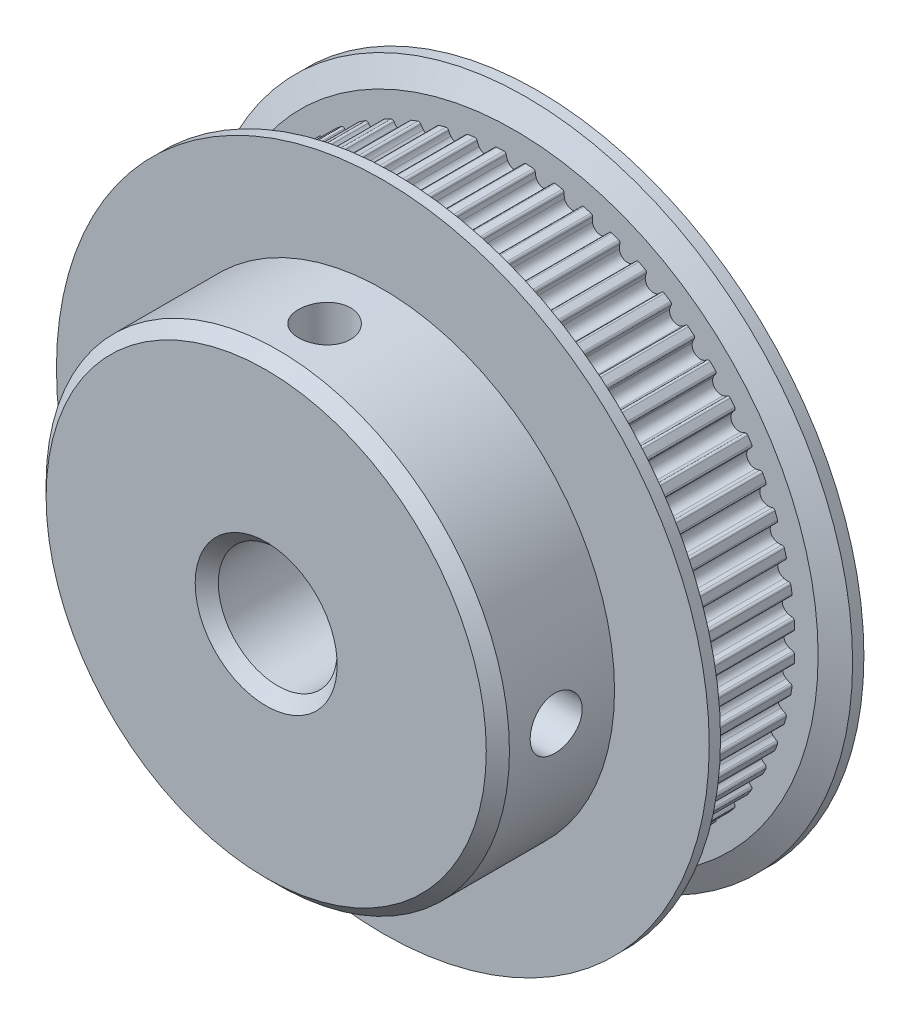
SolidWorks part; units mm, degrees
ref_plane "Front Plane" through (0, 0, 0) normal (0, 0, 1) x (1, 0, 0)
ref_plane "Top Plane" through (0, 0, 0) normal (0, 1, 0) x (1, 0, 0)
ref_plane "Right Plane" through (0, 0, 0) normal (1, 0, 0) x (0, 0, -1)
sketch "Sketch1" plane through (0, 0, 0) normal (0, 0, 1) x (1, 0, 0)
  line L1 (-1.9027, 18.097) -> (1.9027, 18.097) construction
  line L4 (0, 0) -> (0, 18.097) construction
  line L5 (0, 18.097) -> (0, 19.7035) construction
  line L6 (0, 19.101) -> (1.9973, 18.9963) construction
  line L7 (1.9973, 18.9963) -> (2.8966, 18.9017) construction
  line L8 (1.9973, 18.9963) -> (1.9027, 18.097) construction
  line L9 (-1.9973, 18.9963) -> (-1.9027, 18.097) construction
  line L10 (-1.9707, 18.7437) -> (-2.31, 21.971)
  line L11 (-2.31, 21.971) -> (2.31, 21.971)
  line L12 (2.31, 21.971) -> (1.9707, 18.7437)
  circle A0 centre (0, 0) radius 19.101 construction
  circle A1 centre (0, 0) radius 21.971 construction
  circle A2 centre (0, 0) radius 18.847 construction
  arc A3 (-0.4989, 18.4088) -> (0.4989, 18.4088) centre (0, 18.652) ccw
  arc A4 (-0.4989, 18.4088) -> (-0.5897, 18.7039) centre (0.4, 18.847) cw
  arc A5 (-1.9707, 18.7437) -> (-0.7441, 18.8323) centre (0, 0) cw
  arc A6 (-0.5897, 18.7039) -> (-0.7441, 18.8323) centre (-0.7382, 18.6824) ccw
  arc A7 (1.9707, 18.7437) -> (0.7441, 18.8323) centre (0, 0) ccw
  arc A8 (0.5897, 18.7039) -> (0.7441, 18.8323) centre (0.7382, 18.6824) cw
  arc A9 (0.4989, 18.4088) -> (0.5897, 18.7039) centre (-0.4, 18.847) ccw
  point P6 (0, 20.9083)
  point P11 (0, 19.101)
  point P13 (0, 21.971)
  point P14 (0, 18.847)
  dimension "D1" = 1.2049
  dimension "D2" = 0.6025
sketch "Sketch2" plane through (0, 0, 0) normal (1, 0, 0) x (0, 0, -1)
  line L0 (-9.1313, 4) -> (9.1313, 4)
  line L1 (-9.1313, 4) -> (-9.1313, 15.595)
  line L2 (-9.1313, 15.595) -> (-1.2787, 15.595)
  line L3 (-1.2787, 15.595) -> (-1.2787, 21.971)
  line L4 (-1.2787, 21.971) -> (0.2413, 21.971) construction
  line L5 (0.2413, 21.971) -> (0.2413, 18.847) construction
  line L6 (0.2413, 18.847) -> (7.6113, 18.847)
  line L7 (7.6113, 18.847) -> (7.6113, 21.971) construction
  line L8 (7.6113, 21.971) -> (9.1313, 21.971) construction
  line L9 (9.1313, 21.971) -> (9.1313, 4)
  line L10 (-9.1313, 0) -> (9.1313, 0) construction
  line L11 (8.3713, 21.971) -> (7.6113, 20.409)
  line L12 (0.2413, 20.409) -> (-0.5187, 21.971)
  line L13 (-1.2787, 21.971) -> (-0.5187, 21.971)
  line L14 (0.2413, 20.409) -> (0.2413, 18.847)
  line L15 (7.6113, 18.847) -> (7.6113, 20.409)
  line L16 (8.3713, 21.971) -> (9.1313, 21.971)
  arc A0 (0.2413, 20.409) -> (-0.5187, 21.971) centre (-1.7439, 20.409) ccw construction
  arc A1 (7.6113, 20.409) -> (8.3713, 21.971) centre (9.5965, 20.409) cw construction
  point P12 (0.2413, 20.409)
  point P14 (-0.5187, 21.971)
  point P20 (7.6113, 20.409)
  point P21 (8.3713, 21.971)
  point P25 (7.6113, 0)
  point P26 (0.2413, 0)
revolve "Revolve1" add sketch "Sketch2" angle 360 mid plane about L10
sketch "Sketch3" plane through (0, 0, 0) normal (0, 0, 1) x (1, 0, 0)
  line L6 (2.31, 21.971) -> (-2.31, 21.971)
  line L7 (1.9707, 18.7437) -> (2.31, 21.971)
  line L8 (-2.31, 21.971) -> (-1.9707, 18.7437)
  line L9 (2.31, 21.971) -> (-2.31, 21.971)
  line L10 (1.9707, 18.7437) -> (2.31, 21.971)
  line L11 (-2.31, 21.971) -> (-1.9707, 18.7437)
  arc A8 (1.9707, 18.7437) -> (0.7441, 18.8323) centre (0, 0) ccw
  arc A9 (0.7441, 18.8323) -> (0.5897, 18.7039) centre (0.7382, 18.6824) ccw
  arc A10 (0.4989, 18.4088) -> (0.5897, 18.7039) centre (-0.4, 18.847) ccw
  arc A11 (-0.4989, 18.4088) -> (0.4989, 18.4088) centre (0, 18.652) ccw
  arc A12 (-0.5897, 18.7039) -> (-0.4989, 18.4088) centre (0.4, 18.847) ccw
  arc A13 (-0.5897, 18.7039) -> (-0.7441, 18.8323) centre (-0.7382, 18.6824) ccw
  arc A14 (-0.7441, 18.8323) -> (-1.9707, 18.7437) centre (0, 0) ccw
  arc A15 (1.9707, 18.7437) -> (0.7441, 18.8323) centre (0, 0) ccw
  arc A16 (0.7441, 18.8323) -> (0.5897, 18.7039) centre (0.7382, 18.6824) ccw
  arc A17 (0.4989, 18.4088) -> (0.5897, 18.7039) centre (-0.4, 18.847) ccw
  arc A18 (-0.4989, 18.4088) -> (0.4989, 18.4088) centre (0, 18.652) ccw
  arc A19 (-0.5897, 18.7039) -> (-0.4989, 18.4088) centre (0.4, 18.847) ccw
  arc A20 (-0.5897, 18.7039) -> (-0.7441, 18.8323) centre (-0.7382, 18.6824) ccw
  arc A21 (-0.7441, 18.8323) -> (-1.9707, 18.7437) centre (0, 0) ccw
  dimension "D1" = 0
extrude "Cut-Extrude1" cut sketch "Sketch3" against normal up to vertex (7.6113 mm away) from vertex up to point (0, 18.847, -7.6113) starting at point (0, 18.847, -0.2413)
pattern_circular "CirPattern1" count 60 over 360 about axis through (0, 0, 9.1313) along (0, 0, 1) of "Cut-Extrude1"
sketch "Sketch4" plane through (0, 0, 0) normal (1, 0, 0) x (0, -1, 0)
  line L0 (0, -1.2787) -> (0, -9.1313) construction
  line L1 (-15.595, -1.2787) -> (15.595, -1.2787) construction
  line L2 (-15.595, -9.1313) -> (15.595, -9.1313) construction
  circle A0 centre (0, -5.205) radius 1.7526
extrude "Cut-Extrude2" cut sketch "Sketch4" along normal through all
ref_plane "Plane1" through (0, 0, 5.205) normal (0, 0, 1) x (1, 0, 0)
sketch "Sketch5" plane through (0, 0, 5.205) normal (0, 0, 1) x (1, 0, 0)
  line L0 (0, 0.1664) -> (0, 15.595) construction
  line L1 (4, -1.3716) -> (4, 0)
  line L2 (4.381, -1.7526) -> (15.1152, -1.7526)
  line L3 (4, 0) -> (15.595, 0) construction
  line L4 (4, 0) -> (15.4962, 0)
  line L5 (15.4962, 0) -> (15.4962, -1.3716)
  line L6 (4.381, -1.7526) -> (4, -1.3716)
  line L7 (15.4962, -1.3716) -> (15.1152, -1.7526)
  circle A0 centre (0, 0) radius 15.595 construction
  circle A1 centre (0, 0) radius 4 construction
  point P2 (4, -1.7526)
  point P11 (15.4962, -1.7526)
revolve "Revolve2" [suppressed] add sketch "Sketch5" angle 360 mid plane about L4
sketch "Sketch6" [suppressed] plane through (15.4207, 5.3841, 0) normal (-1, 0, 0) x (0, -1, 0)
  line L1 (5.3841, 6.2169) -> (4.5078, 5.7109)
  line L2 (4.5078, 5.7109) -> (4.5078, 4.6991)
  line L3 (4.5078, 4.6991) -> (5.3841, 4.1931)
  line L4 (5.3841, 4.1931) -> (6.2604, 4.6991)
  line L5 (6.2604, 4.6991) -> (6.2604, 5.7109)
  line L6 (6.2604, 5.7109) -> (5.3841, 6.2169)
  circle A0 centre (5.3841, 5.205) radius 0.8763 construction
  dimension "D1" = 1.7526
extrude "Cut-Extrude3" [suppressed] cut sketch "Sketch6" along normal blind 1.3144
pattern_circular "CirPattern2" count 2 every 90 about axis through (0, 0, 9.1313) along (0, 0, 1) of "Cut-Extrude2", "Revolve2", "Cut-Extrude3"
chamfer "Chamfer1" distance 0.7798 angle 45 2 edges at (4, 0, 9.1313) (15.595, 0, 9.1313)
ref_axis "Center Axis 1" through (0, 0, -9.1313) along (0, 0, 1)
ref_plane "Contact Plane 1" through (0, 0, 9.1313) normal (0, 0, 1) x (1, 0, 0)
ref_plane "Contact Plane 2" through (0, 0, -9.1313) normal (0, 0, -1) x (-1, 0, 0)
sketch "Sketch7" plane through (0, 0, 9.1313) normal (0, 0, 1) x (1, 0, 0)
  circle A0 centre (0, 0) radius 4.175
  dimension "D1" = 8.35
equation "\"D2@Sketch1\" = \"D1@Sketch1\"/2"
equation "\"D1@Sketch6\" = \"Set Screw@Sketch4\" / 2"
equation "\"D1@Cut-Extrude3\" = \"D1@Sketch6\"*.75"
equation "\"D1@Chamfer1\"=\"Hub Dia@Sketch2\"*.025"
